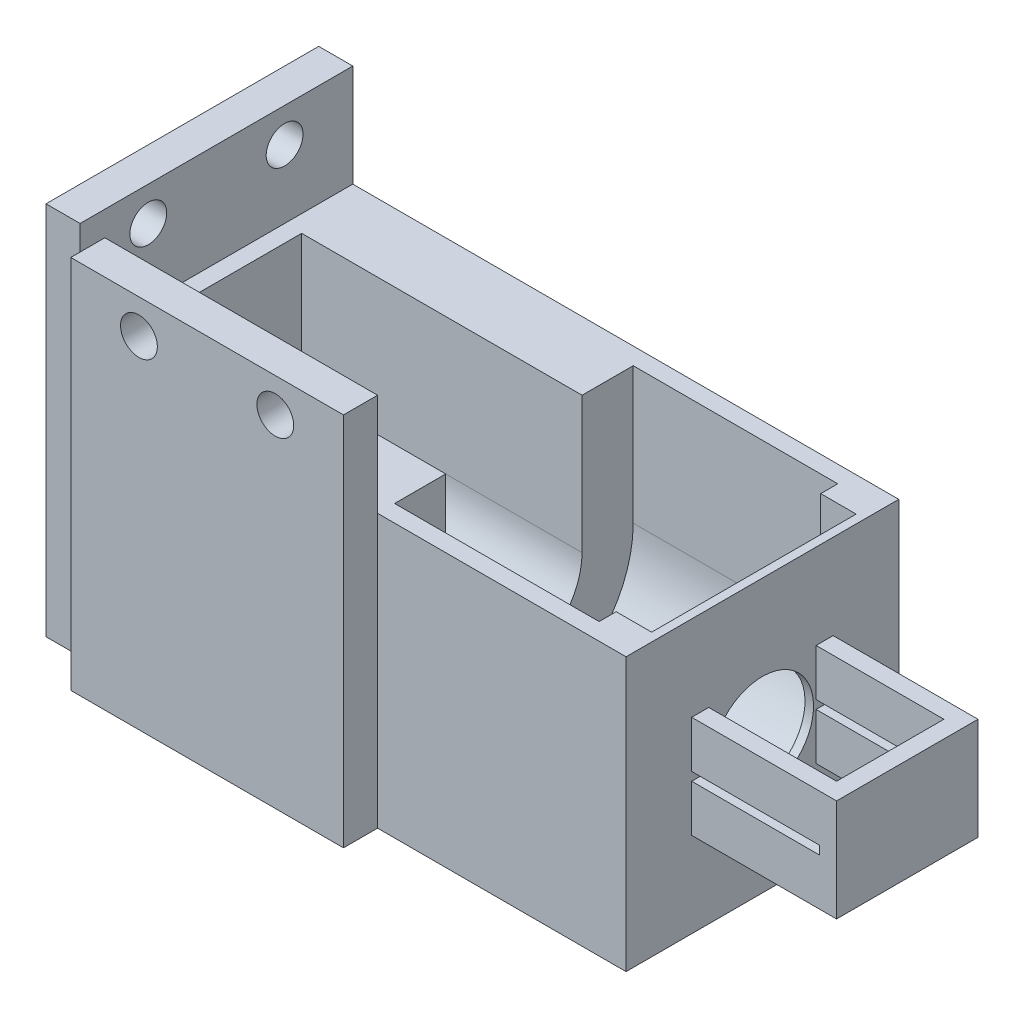
SolidWorks part; units mm, degrees
ref_plane "Front Plane" through (0, 0, 0) normal (0, 0, 1) x (1, 0, 0)
ref_plane "Top Plane" through (0, 0, 0) normal (0, 1, 0) x (1, 0, 0)
ref_plane "Right Plane" through (0, 0, 0) normal (1, 0, 0) x (0, 0, -1)
sketch "Sketch1" plane through (0, 0, 0) normal (0, 0, 1) x (1, 0, 0)
  line L1 (-76.2, -50.8) -> (40.64, -50.8)
  line L2 (-76.2, -50.8) -> (-76.2, 0)
  line L3 (-76.2, 0) -> (40.64, 0)
  line L4 (40.64, -50.8) -> (40.64, 0)
  line L5 (-76.2, -50.8) -> (40.64, 0) construction
  line L6 (-76.2, 0) -> (40.64, -50.8) construction
  point P0 (0, 0)
  dimension "D1" = 116.84
  dimension "D2" = 50.8
  dimension "D3" = 76.2
extrude "Boss-Extrude1" add sketch "Sketch1" along normal mid plane 50.8
sketch "Sketch2" plane through (0, 0, 0) normal (0, 0, 1) x (1, 0, 0)
  line L0 (-152.4829, -25.4) -> (19.6294, -25.4) construction
  line L1 (-49.3609, -3.175) -> (-49.3609, -12.7)
  line L2 (40.64, 0) -> (-76.2, 0) construction
  line L3 (40.64, 0) -> (-76.2, 0) construction
  line L4 (-11.2609, -3.175) -> (-11.2609, -6.35)
  line L5 (-11.2609, -25.4) -> (-11.2609, -3.175) construction
  line L6 (-128.4172, -25.4) -> (-157.8092, -25.4)
  line L7 (19.6294, -25.4) -> (20.7431, -25.4)
  line L8 (-607.3619, -25.4) -> (19.6294, -25.4) construction
  line L9 (-49.3609, -3.175) -> (-11.2609, -3.175)
  line L10 (19.6294, -25.4) -> (-128.4172, -25.4)
  line L11 (-11.2609, -6.35) -> (-4.6569, -6.35)
  line L12 (-4.6569, -6.35) -> (-4.6569, -15.494)
  line L13 (-4.6569, -15.494) -> (20.7431, -15.494)
  line L14 (-49.3609, -12.7) -> (-220.2024, -12.7)
  line L15 (-220.2024, -12.7) -> (-220.2024, -25.4)
  line L16 (-220.2024, -25.4) -> (-157.8092, -25.4)
  line L20 (20.7431, -15.494) -> (20.7431, -25.4)
  line L21 (-76.2, 0) -> (-76.2, -50.8) construction
  point P23 (-11.2609, -25.4)
  dimension "D1" = 22.225
  dimension "D2" = 38.1
  dimension "D3" = 25.4
  dimension "D4" = 32.004
  dimension "D5" = 9.906
  dimension "D6" = 3.175
  dimension "D7" = 26.8391
  dimension "D8" = 25.4
  dimension "D9" = 12.7
revolve "Cut-Revolve1" cut sketch "Sketch2" angle 360 about L0
sketch "Sketch38" plane through (20.7431, 0, 0) normal (1, 0, 0) x (0, 0, -1)
  line L1 (-10, -35.4) -> (10, -35.4)
  line L2 (-10, -35.4) -> (-10, -15.4)
  line L3 (-10, -15.4) -> (10, -15.4)
  line L4 (10, -35.4) -> (10, -15.4)
  line L5 (-10, -35.4) -> (10, -15.4) construction
  line L6 (-10, -15.4) -> (10, -35.4) construction
  circle A0 centre (0, -25.4) radius 9.906 construction
  point P1 (0, -25.4)
  dimension "D1" = 20
  dimension "D2" = 20
extrude "Cut-Extrude33" cut sketch "Sketch38" against normal offset from surface (23.8125 mm away) 1.5875 up to face at (-4.6569, -25.4, 19.05)
sketch "Sketch37" plane through (40.64, 0, 0) normal (1, 0, 0) x (0, 0, -1)
  line L0 (25.4, -50.8) -> (25.4, 0) construction
  line L1 (-25.4, 0) -> (25.4, 0)
  line L2 (-25.4, 0) -> (-25.4, -25.4)
  line L3 (-25.4, -25.4) -> (25.4, -25.4)
  line L4 (25.4, 0) -> (25.4, -25.4)
  line L5 (10, -35.4) -> (10, -15.4) construction
  point P7 (0, -25.4)
  point P11 (0, 0)
  point P14 (10, -25.4)
extrude "Cut-Extrude32" cut sketch "Sketch37" against normal through all
sketch "Sketch39" plane through (0, -25.4, 0) normal (0, 1, 0) x (1, 0, 0)
  line L24 (-49.3609, -12.7) -> (-76.2, -12.7)
  line L25 (-76.2, -12.7) -> (-76.2, -25.4)
  line L26 (-76.2, -25.4) -> (40.64, -25.4)
  line L27 (40.64, -25.4) -> (40.64, 25.4)
  line L28 (40.64, 25.4) -> (-76.2, 25.4)
  line L29 (-76.2, 25.4) -> (-76.2, 12.7)
  line L30 (-76.2, 12.7) -> (-49.3609, 12.7)
  line L31 (-49.3609, 12.7) -> (-49.3609, 22.225)
  line L32 (-49.3609, 22.225) -> (-11.2609, 22.225)
  line L33 (-11.2609, 22.225) -> (-11.2609, 19.05)
  line L34 (-11.2609, 19.05) -> (-4.6569, 19.05)
  line L35 (-4.6569, 19.05) -> (-4.6569, 9.906)
  line L36 (-4.6569, 9.906) -> (-3.0694, 9.906)
  line L37 (-3.0694, 9.906) -> (-3.0694, 10)
  line L38 (-3.0694, 9.906) -> (-3.0694, 10)
  line L39 (20.7431, 10) -> (20.7431, -10)
  line L40 (-3.0694, 10) -> (20.7431, 10)
  line L41 (-3.0694, 10) -> (20.7431, 10)
  line L42 (-3.0694, -9.906) -> (-4.6569, -9.906)
  line L43 (-4.6569, -9.906) -> (-4.6569, -19.05)
  line L44 (-4.6569, -19.05) -> (-11.2609, -19.05)
  line L45 (-11.2609, -19.05) -> (-11.2609, -22.225)
  line L46 (-11.2609, -22.225) -> (-49.3609, -22.225)
  line L47 (-49.3609, -22.225) -> (-49.3609, -12.7)
  line L48 (-49.3609, -12.7) -> (-76.2, -12.7)
  line L49 (-76.2, -12.7) -> (-76.2, -25.4)
  line L50 (-76.2, -25.4) -> (40.64, -25.4)
  line L51 (40.64, -25.4) -> (40.64, 25.4)
  line L52 (40.64, 25.4) -> (-76.2, 25.4)
  line L53 (-76.2, 25.4) -> (-76.2, 12.7)
  line L54 (-76.2, 12.7) -> (-49.3609, 12.7)
  line L55 (-49.3609, 12.7) -> (-49.3609, 22.225)
  line L56 (-49.3609, 22.225) -> (-11.2609, 22.225)
  line L57 (-11.2609, 22.225) -> (-11.2609, 19.05)
  line L58 (-11.2609, 19.05) -> (-4.6569, 19.05)
  line L59 (-4.6569, 19.05) -> (-4.6569, 9.906)
  line L60 (-4.6569, 9.906) -> (-3.0694, 9.906)
  line L61 (20.7431, -10) -> (-3.0694, -10)
  line L62 (20.7431, -10) -> (-3.0694, -10)
  line L63 (20.7431, 10) -> (20.7431, -10)
  line L64 (-3.0694, -10) -> (-3.0694, -9.906)
  line L65 (-3.0694, -10) -> (-3.0694, -9.906)
  line L66 (-3.0694, -9.906) -> (-4.6569, -9.906)
  line L67 (-4.6569, -9.906) -> (-4.6569, -19.05)
  line L68 (-4.6569, -19.05) -> (-11.2609, -19.05)
  line L69 (-11.2609, -19.05) -> (-11.2609, -22.225)
  line L70 (-11.2609, -22.225) -> (-49.3609, -22.225)
  line L71 (-49.3609, -22.225) -> (-49.3609, -12.7)
  dimension "D1" = 0
extrude "Boss-Extrude5" add sketch "Sketch39" along normal blind 25.4
ref_axis "Axis1" through (-3.0694, -25.4, 0) along (-1, 0, 0)
ref_plane "Plane_Mid" through (0, -25.4, 0) normal (0, 1, 0) x (1, 0, 0)
sketch "Sketch45" plane through (0, 0, 0) normal (0, 0, 1) x (1, 0, 0)
  line L2 (40.64, 0) -> (-3.0694, 0)
  line L4 (40.64, 0) -> (40.64, -19.05)
  line L5 (40.64, -19.05) -> (-3.0694, -19.05)
  line L6 (-3.0694, -25.4) -> (-4.6569, -25.4) construction
  line L8 (-3.0694, 0) -> (-3.0694, -19.05)
  dimension "D2" = 6.35
extrude "Cut-Extrude54" cut sketch "Sketch45" against normal through all both and the other way through all
sketch "Sketch53" plane through (20.7431, 0, 0) normal (-1, 0, 0) x (0, 0, 1)
  circle A0 centre (0, -25.4) radius 2
  dimension "D1" = 4
extrude "Cut-Extrude46" cut sketch "Sketch53" against normal blind 0.0254
sketch "Sketch72" plane through (0, -19.05, 0) normal (0, 1, 0) x (1, 0, 0)
  line L0 (-3.0694, -25.4) -> (-3.0694, -13.175)
  line L1 (-3.0694, -10) -> (-3.0694, -25.4) construction
  line L2 (-3.0694, -13.175) -> (23.9181, -13.175)
  line L3 (23.9181, -13.175) -> (23.9181, 13.175)
  line L4 (23.9181, 13.175) -> (-3.0694, 13.175)
  line L5 (-3.0694, 25.4) -> (-3.0694, 10) construction
  line L6 (-3.0694, 13.175) -> (-3.0694, 25.4)
  line L7 (-3.0694, 25.4) -> (40.64, 25.4)
  line L8 (40.64, 25.4) -> (40.64, -25.4)
  line L9 (40.64, -25.4) -> (-3.0694, -25.4)
  line L10 (-3.0694, -10) -> (20.7431, -10) construction
  line L11 (-3.0694, -10) -> (-3.0694, -13.175) construction
  line L12 (20.7431, -10) -> (23.9181, -10) construction
  line L13 (20.7431, 10) -> (20.7431, 13.175) construction
  dimension "D1" = 3.175
extrude "Cut-Extrude55" cut sketch "Sketch72" against normal through all
sketch "Sketch61" plane through (-4.6569, 0, 0) normal (-1, 0, 0) x (0, 0, 1)
  circle A0 centre (0, -25.4) radius 9.525
  circle A1 centre (0, -25.4) radius 9.906
  arc A2 (-9.906, -25.4) -> (9.906, -25.4) centre (0, -25.4) ccw construction
  dimension "D1" = 19.05
extrude "Boss-Extrude11" add sketch "Sketch61" against normal up to surface (1.5875 mm away) up to face at (-3.0694, -25.6816, 0)
sketch "Sketch70" plane through (0, 0, 0) normal (0, 1, 0) x (1, 0, 0)
  line L1 (-4.6569, 9.906) -> (-3.0694, 9.906)
  line L2 (-4.6569, 9.906) -> (-4.6569, -9.906)
  line L3 (-4.6569, -9.906) -> (-3.0694, -9.906)
  line L4 (-3.0694, 9.906) -> (-3.0694, -9.906)
extrude "Boss-Extrude17" add sketch "Sketch70" against normal up to next
sketch "Sketch76" plane through (0, -35.4, 0) normal (0, 1, 0) x (1, 0, 0)
  line L5 (-3.0694, -10) -> (20.7431, -10)
  line L6 (20.7431, -10) -> (20.7431, 10)
  line L9 (20.7431, 10) -> (-3.0694, 10)
  line L10 (-3.0694, 10) -> (-3.0694, -10)
  line L11 (-3.0694, -10) -> (20.7431, -10)
  line L12 (20.7431, -10) -> (20.7431, 10)
  line L13 (20.7431, 10) -> (-3.0694, 10)
  line L14 (-3.0694, 10) -> (-3.0694, -10)
  dimension "D1" = 0
extrude "Cut-Extrude58" cut sketch "Sketch76" against normal through all
sketch "Sketch77" plane through (0, 0, 0) normal (0, 0, 1) x (1, 0, 0)
  line L1 (-3.0694, -26.1938) -> (20.7431, -26.1938)
  line L2 (-3.0694, -26.1938) -> (-3.0694, -24.6063)
  line L3 (-3.0694, -24.6063) -> (20.7431, -24.6063)
  line L4 (20.7431, -26.1938) -> (20.7431, -24.6063)
  line L5 (-3.0694, -26.1938) -> (20.7431, -24.6063) construction
  line L6 (-3.0694, -24.6063) -> (20.7431, -26.1938) construction
  line L9 (-3.0694, -25.4) -> (-4.6569, -25.4) construction
  line L10 (-3.0694, -19.05) -> (-3.0694, -50.8) construction
  line L11 (20.7431, -19.05) -> (20.7431, -50.8) construction
  point P0 (8.8368, -25.4)
  dimension "D2" = 1.5875
extrude "Cut-Extrude59" cut sketch "Sketch77" against normal through all both and the other way through all
sketch "Sketch78" plane through (-76.2, 0, 0) normal (-1, 0, 0) x (0, 0, 1)
  line L7 (25.4, -50.8) -> (25.4, 0)
  line L8 (25.4, 0) -> (12.7, 0)
  line L9 (12.7, 0) -> (12.7, -25.4)
  line L10 (-12.7, -25.4) -> (-12.7, 0)
  line L11 (-12.7, 0) -> (-25.4, 0)
  line L12 (-25.4, 0) -> (-25.4, -50.8)
  line L13 (-25.4, -50.8) -> (25.4, -50.8)
  line L14 (25.4, -50.8) -> (25.4, 0)
  line L15 (25.4, 0) -> (12.7, 0)
  line L16 (12.7, 0) -> (12.7, -25.4)
  line L17 (-12.7, -25.4) -> (-12.7, 0)
  line L18 (-12.7, 0) -> (-25.4, 0)
  line L19 (-25.4, 0) -> (-25.4, -50.8)
  line L20 (-25.4, -50.8) -> (25.4, -50.8)
  arc A1 (-12.7, -25.4) -> (12.7, -25.4) centre (0, -25.4) ccw
  arc A2 (-12.7, -25.4) -> (12.7, -25.4) centre (0, -25.4) ccw
  dimension "D1" = 0
sketch "Sketch86" plane through (0, -19.05, 0) normal (0, 1, 0) x (1, 0, 0)
  line L16 (20.7431, 10) -> (20.7431, -10)
  line L25 (20.7431, -10) -> (-3.0694, -10)
  line L26 (-3.0694, -10) -> (-3.0694, -13.175)
  line L27 (-3.0694, -13.175) -> (23.9181, -13.175)
  line L28 (23.9181, -13.175) -> (23.9181, 13.175)
  line L29 (23.9181, 13.175) -> (-3.0694, 13.175)
  line L30 (-3.0694, 13.175) -> (-3.0694, 10)
  line L31 (-3.0694, 10) -> (20.7431, 10)
  line L32 (20.7431, 10) -> (20.7431, -10)
  line L41 (20.7431, -10) -> (-3.0694, -10)
  line L42 (-3.0694, -10) -> (-3.0694, -13.175)
  line L43 (-3.0694, -13.175) -> (23.9181, -13.175)
  line L44 (23.9181, -13.175) -> (23.9181, 13.175)
  line L45 (23.9181, 13.175) -> (-3.0694, 13.175)
  line L46 (-3.0694, 13.175) -> (-3.0694, 10)
  line L47 (-3.0694, 10) -> (20.7431, 10)
  dimension "D1" = 0
extrude "Boss-Extrude24" add sketch "Sketch86" along normal blind 3.175
extrude "Boss-Extrude18" add sketch "Sketch78" along normal blind 25.4
sketch "Sketch79" plane through (-101.6, 0, 0) normal (-1, 0, 0) x (0, 0, 1)
  line L1 (-25.4, -50.8) -> (25.4, -50.8)
  line L2 (-25.4, -50.8) -> (-25.4, 0)
  line L3 (-25.4, 0) -> (25.4, 0)
  line L4 (25.4, -50.8) -> (25.4, 0)
extrude "Boss-Extrude19" add sketch "Sketch79" along normal blind 3.175
sketch "Sketch80" plane through (-104.775, 0, 0) normal (-1, 0, 0) x (0, 0, 1)
  line L0 (-25.4, 0) -> (-25.4, -50.8) construction
  line L1 (25.4, -50.8) -> (-25.4, -50.8)
  line L2 (25.4, -50.8) -> (25.4, 50.8)
  line L3 (25.4, 50.8) -> (-25.4, 50.8)
  line L4 (-25.4, -50.8) -> (-25.4, 50.8)
  line L5 (25.4, 0) -> (-25.4, 0) construction
  dimension "D1" = 50.8
extrude "Boss-Extrude20" add sketch "Sketch80" along normal blind 6.35
sketch "Sketch81" plane through (-104.775, 0, 0) normal (1, 0, 0) x (0, 0, -1)
  line L0 (-25.4, 50.8) -> (25.4, 50.8) construction
  line L1 (-25.4, 0) -> (-25.4, 50.8) construction
  circle A0 centre (-12.7, 38.1) radius 3.429
  circle A1 centre (12.7, 38.1) radius 3.429
  circle A2 centre (12.7, 12.7) radius 3.429
  circle A3 centre (-12.7, 12.7) radius 3.429
  dimension "D1" = 6.858
  dimension "D2" = 12.7
  dimension "D3" = 12.7
  dimension "D4" = 2
  dimension "D5" = 2
extrude "Cut-Extrude60" cut sketch "Sketch81" against normal through all
sketch "Sketch82" plane through (0, 0, 25.4) normal (0, 0, 1) x (1, 0, 0)
  line L0 (-111.125, -50.8) -> (-3.0694, -50.8) construction
  line L1 (-100.1609, -50.8) -> (-49.3609, -50.8)
  line L2 (-100.1609, -50.8) -> (-100.1609, 50.8)
  line L3 (-100.1609, 50.8) -> (-49.3609, 50.8)
  line L4 (-49.3609, -50.8) -> (-49.3609, 50.8)
  line L5 (-111.125, 50.8) -> (-104.775, 50.8) construction
  dimension "D1" = 50.8
extrude "Boss-Extrude21" add sketch "Sketch82" along normal blind 6.35
sketch "Sketch83" plane through (0, 0, 25.4) normal (0, 0, -1) x (-1, 0, 0)
  line L0 (49.3609, 50.8) -> (100.1609, 50.8) construction
  line L1 (49.3609, 0) -> (49.3609, 50.8) construction
  circle A0 centre (62.0609, 38.1) radius 3.429
  circle A1 centre (87.4609, 38.1) radius 3.429
  circle A2 centre (87.4609, 12.7) radius 3.429
  circle A3 centre (62.0609, 12.7) radius 3.429
  dimension "D1" = 6.858
  dimension "D2" = 12.7
  dimension "D3" = 12.7
  dimension "D4" = 2
  dimension "D5" = 2
extrude "Cut-Extrude61" cut sketch "Sketch83" against normal through all
sketch "Sketch84" plane through (0, 50.8, 0) normal (0, 1, 0) x (1, 0, 0)
  line L1 (-129.7202, -53.2466) -> (-19.4704, -53.2466)
  line L2 (-129.7202, -53.2466) -> (-129.7202, 56.3815)
  line L3 (-129.7202, 56.3815) -> (-19.4704, 56.3815)
  line L4 (-19.4704, -53.2466) -> (-19.4704, 56.3815)
extrude "Cut-Extrude62" cut sketch "Sketch84" against normal blind 31.75
sketch "Sketch87" plane through (0, -50.8, 0) normal (0, -1, 0) x (1, 0, 0)
  line L1 (23.9181, 13.175) -> (-3.0694, 13.175)
  line L2 (23.9181, 13.175) -> (23.9181, -25.4)
  line L3 (23.9181, -25.4) -> (-3.0694, -25.4)
  line L4 (-3.0694, 13.175) -> (-3.0694, -25.4)
  line L5 (23.9181, 13.175) -> (-3.0694, -25.4) construction
  line L6 (23.9181, -25.4) -> (-3.0694, 13.175) construction
  point P4 (10.4243, -6.1125)
extrude "Cut-Extrude63" cut sketch "Sketch87" against normal blind 15.875
sketch "Sketch89" plane through (0, 0, 0) normal (0, 1, 0) x (1, 0, 0)
  line L0 (-3.0694, 0) -> (-4.6569, 0) construction
  line L1 (-38.3605, -2.5981) -> (-18.7213, -2.5981)
  line L2 (-38.3605, -2.5981) -> (-38.3605, 2.5981)
  line L3 (-38.3605, 2.5981) -> (-18.7213, 2.5981)
  line L4 (-18.7213, -2.5981) -> (-18.7213, 2.5981)
  line L5 (-38.3605, -2.5981) -> (-18.7213, 2.5981) construction
  line L6 (-38.3605, 2.5981) -> (-18.7213, -2.5981) construction
  line L8 (-84.575, -2.5981) -> (-64.9357, -2.5981)
  line L9 (-84.575, -2.5981) -> (-84.575, 2.5981)
  line L10 (-84.575, 2.5981) -> (-64.9357, 2.5981)
  line L11 (-64.9357, -2.5981) -> (-64.9357, 2.5981)
  line L12 (-84.575, -2.5981) -> (-64.9357, 2.5981) construction
  line L13 (-84.575, 2.5981) -> (-64.9357, -2.5981) construction
  point P4 (-28.5409, 0)
  point P13 (-74.7553, 0)
extrude "Cut-Extrude64" cut sketch "Sketch89" against normal through all
